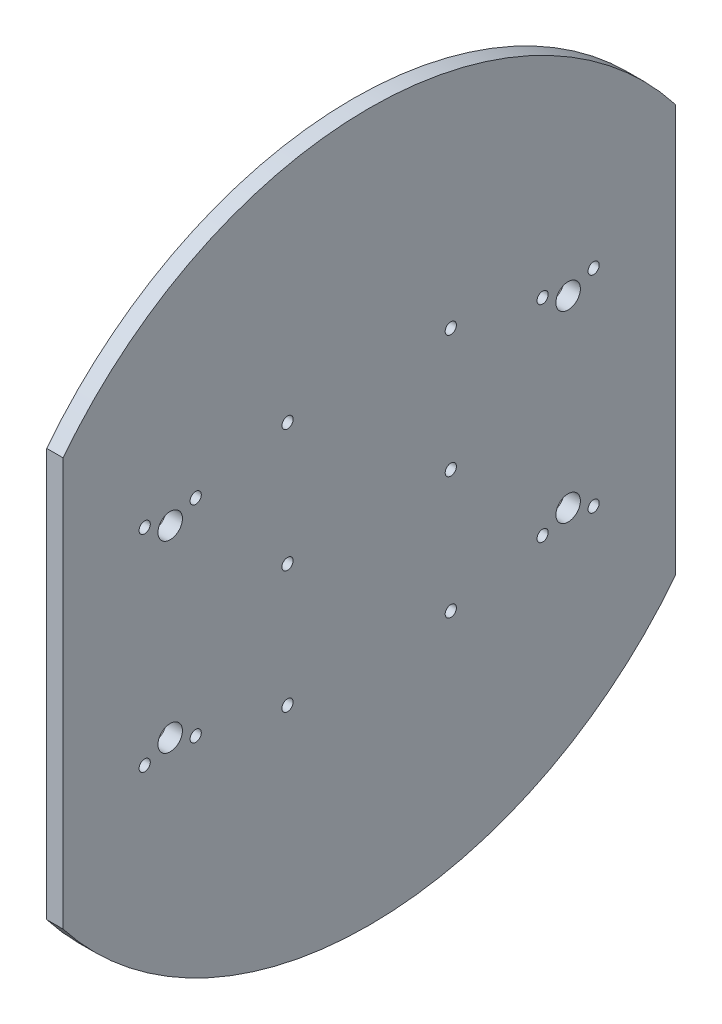
SolidWorks part; units mm, degrees
ref_plane "前视基准面" through (0, 0, 0) normal (0, 0, 1) x (1, 0, 0)
ref_plane "上视基准面" through (0, 0, 0) normal (0, 1, 0) x (1, 0, 0)
ref_plane "右视基准面" through (0, 0, 0) normal (1, 0, 0) x (0, 0, -1)
other "Configuration Table"
sketch "草图1" plane through (0, 0, 0) normal (1, 0, 0) x (0, 0, -1)
  line L0 (0, 0) -> (50000, 0) construction
  line L2 (-150, 100) -> (-150, -100)
  line L4 (150, 100) -> (150, -100)
  arc A0 (150, 100) -> (-150, 100) centre (0, -16.619) ccw
  arc A1 (150, -100) -> (-150, -100) centre (0, 16.619) cw
  dimension "D1" = 150
  dimension "D4" = 190
  dimension "D2" = 200
  dimension "D5" = 300
extrude "凸台-拉伸1" add sketch "草图1" along normal blind 8
sketch "草图2" plane through (8, 0, 0) normal (1, 0, 0) x (0, 0, -1)
  line L0 (97.5, 45) -> (97.5, -45) construction
  line L1 (0, 0) -> (0, 50000) construction
  line L2 (85, 50.5) -> (110, 50.5) construction
  line L3 (85, 50.5) -> (85, -50.5) construction
  line L4 (85, -50.5) -> (110, -50.5) construction
  line L5 (110, 50.5) -> (110, -50.5) construction
  line L6 (-110, 50.5) -> (-110, -50.5) construction
  line L7 (-85, -50.5) -> (-110, -50.5) construction
  line L8 (-85, 50.5) -> (-85, -50.5) construction
  line L9 (-85, 50.5) -> (-110, 50.5) construction
  line L10 (-97.5, 45) -> (-97.5, -45) construction
  circle A0 centre (97.5, 45) radius 6
  circle A1 centre (97.5, -45) radius 6
  circle A2 centre (85, 50.5) radius 2.75
  circle A3 centre (110, 50.5) radius 2.75
  circle A4 centre (85, -50.5) radius 2.75
  circle A5 centre (110, -50.5) radius 2.75
  circle A6 centre (-110, -50.5) radius 2.75
  circle A7 centre (-85, -50.5) radius 2.75
  circle A8 centre (-110, 50.5) radius 2.75
  circle A9 centre (-85, 50.5) radius 2.75
  circle A10 centre (-97.5, -45) radius 6
  circle A11 centre (-97.5, 45) radius 6
  point P9 (97.5, 0)
  dimension "D4" = 12
  dimension "D5" = 12
  dimension "D10" = 5.5
  dimension "D1" = 90
  dimension "D2" = 97.5
  dimension "D3" = 45
  dimension "D6" = 25
  dimension "D7" = 12.5
  dimension "D8" = 101
  dimension "D9" = 50.5
extrude "切除-拉伸1" cut sketch "草图2" against normal blind 8
sketch "草图3" plane through (8, 0, 0) normal (1, 0, 0) x (0, 0, -1)
  line L1 (-40, 60) -> (40, 60) construction
  line L2 (-40, 60) -> (-40, -60) construction
  line L3 (-40, -60) -> (40, -60) construction
  line L4 (40, 60) -> (40, -60) construction
  circle A0 centre (-40, 60) radius 2.75
  circle A2 centre (40, 60) radius 2.75
  circle A3 centre (40, -60) radius 2.75
  circle A5 centre (-40, -60) radius 2.75
  circle A6 centre (40, 0) radius 2.75
  circle A7 centre (-40, 0) radius 2.75
  dimension "D5" = 5.5
  dimension "D6" = 5.5
  dimension "D1" = 120
  dimension "D2" = 80
  dimension "D3" = 60
  dimension "D4" = 40
extrude "切除-拉伸2" cut sketch "草图3" against normal blind 10
